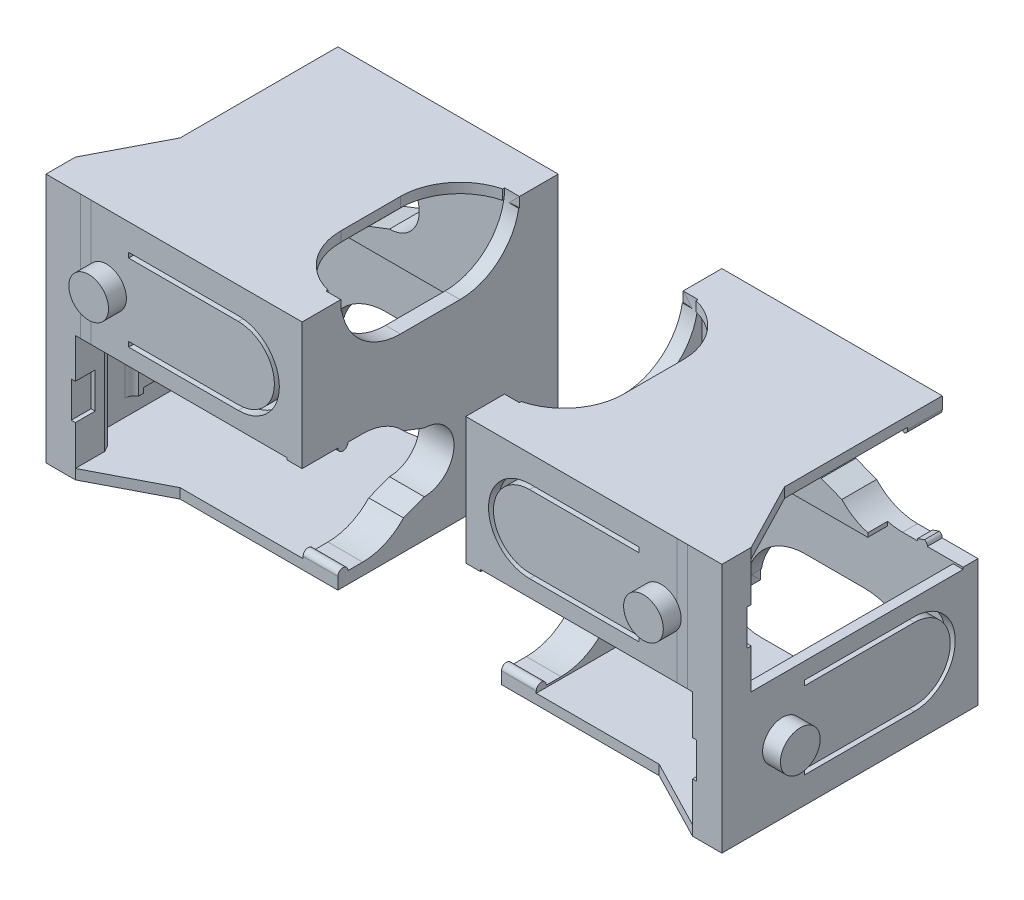
SolidWorks part; units mm, degrees
ref_plane "正面" through (0, 0, 0) normal (0, 0, 1) x (1, 0, 0)
ref_plane "平面" through (0, 0, 0) normal (0, 1, 0) x (1, 0, 0)
ref_plane "右側面" through (0, 0, 0) normal (1, 0, 0) x (0, 0, -1)
sketch "ｽｹｯﾁ1" plane through (0, 0, -3.3889) normal (0, 0, -1) x (-1, 0, 0)
  line L1 (-27.9423, 19.7214) -> (-37.3187, 19.7214) construction
  line L2 (-23.8289, 15.9214) -> (-21.7423, 16.7214)
  line L3 (-21.7423, 22.7214) -> (-23.8289, 23.5214)
  line L4 (-23.8289, 15.9214) -> (-21.7423, 16.7214)
  line L5 (-21.7423, 22.7214) -> (-23.8289, 23.5214)
  line L6 (-27.9423, 26.3214) -> (-30.4423, 26.3214)
  line L7 (-27.9423, 26.3214) -> (-8.2423, 26.3214)
  line L8 (-30.4423, 26.3214) -> (-30.4423, 25.3214)
  line L9 (-29.4213, 25.3214) -> (-27.9423, 25.3214)
  line L10 (-30.4423, 13.9214) -> (-30.4423, 14.1214)
  line L11 (-29.4213, 14.1214) -> (-27.9423, 14.1214)
  line L12 (-27.9423, 13.9214) -> (-30.4423, 13.9214)
  line L13 (-11.7423, 13.9214) -> (-32.5423, 13.9214) construction
  line L14 (-8.2423, 13.9214) -> (-8.2423, 25.5214)
  line L15 (-8.2423, 25.5214) -> (-8.2423, 26.3214)
  line L17 (-33.5423, 13.9214) -> (-9.7423, 13.9214) construction
  line L18 (-27.9423, 13.9214) -> (-9.7423, 13.9214)
  line L20 (-9.7423, 13.9214) -> (-8.2423, 13.9214)
  arc A0 (-27.9423, 14.1214) -> (-23.8289, 15.9214) centre (-27.9423, 19.7214) ccw
  arc A1 (-30.4423, 25.3214) -> (-29.4213, 25.3214) centre (-29.9318, 25.3214) ccw
  arc A2 (-23.8289, 23.5214) -> (-23.8289, 15.9214) centre (-27.9423, 19.7214) ccw
  arc A3 (-21.7423, 16.7214) -> (-21.7423, 22.7214) centre (-21.7423, 19.7214) ccw
  arc A4 (-23.8289, 23.5214) -> (-27.9423, 25.3214) centre (-27.9423, 19.7214) ccw
  arc A5 (-21.7423, 16.7214) -> (-21.7423, 22.7214) centre (-21.7423, 19.7214) ccw
  arc A6 (-30.4423, 14.1214) -> (-29.4213, 14.1214) centre (-29.9318, 14.1214) cw
  dimension "D1" = 0
extrude "ﾎﾞｽ - 押し出し1" add sketch "ｽｹｯﾁ1" against normal up to surface (3.5 mm away)
sketch "ｽｹｯﾁ2" plane through (0, 0, -3.3889) normal (0, 0, -1) x (-1, 0, 0)
  line L0 (-8.2423, 13.9214) -> (-8.2423, 26.3214) construction
  line L1 (-34.0423, 13.9214) -> (-8.2423, 13.9214)
  line L2 (-34.0423, 13.9214) -> (-34.0423, 1.3214)
  line L3 (-34.0423, 1.3214) -> (-8.2423, 1.3214)
  line L4 (-8.2423, 13.9214) -> (-8.2423, 1.3214)
  line L5 (-11.7423, 2.3214) -> (-32.5423, 2.3214) construction
  line L6 (-32.5423, 2.3214) -> (-32.5423, 13.9214) construction
  line L7 (-32.5423, 2.3214) -> (-32.5423, 13.9214) construction
  dimension "D1" = 0
  dimension "D2" = 1
  dimension "D3" = 1.5
extrude "ﾎﾞｽ - 押し出し2" add sketch "ｽｹｯﾁ2" against normal up to vertex (1.5 mm away)
sketch "ｽｹｯﾁ3" plane through (8.2423, 0, 0) normal (-1, 0, 0) x (0, 0, 1)
  line L0 (16.3111, 8.1214) -> (25.6875, 8.1214) construction
  line L1 (12.1977, 11.9214) -> (10.1111, 11.1214)
  line L2 (10.1111, 5.1214) -> (12.1977, 4.3214)
  line L3 (16.3111, 1.5214) -> (18.8111, 1.5214)
  line L4 (16.3111, 1.5214) -> (-3.3889, 1.5214)
  line L5 (18.8111, 1.5214) -> (18.8111, 2.5214)
  line L6 (17.7901, 2.5214) -> (16.3111, 2.5214)
  line L7 (18.8111, 13.9214) -> (18.8111, 13.7214)
  line L8 (17.7901, 13.7214) -> (16.3111, 13.7214)
  line L9 (16.3111, 13.9214) -> (18.8111, 13.9214)
  line L10 (-3.3889, 13.9214) -> (-3.3889, 2.3214)
  line L11 (-3.3889, 2.3214) -> (-3.3889, 1.5214)
  line L12 (16.3111, 13.9214) -> (-1.8889, 13.9214)
  line L13 (-1.8889, 13.9214) -> (-3.3889, 13.9214)
  arc A0 (16.3111, 13.7214) -> (12.1977, 11.9214) centre (16.3111, 8.1214) ccw
  arc A1 (18.8111, 2.5214) -> (17.7901, 2.5214) centre (18.3006, 2.5214) ccw
  arc A2 (12.1977, 4.3214) -> (16.3111, 2.5214) centre (16.3111, 8.1214) ccw
  arc A3 (10.1111, 11.1214) -> (10.1111, 5.1214) centre (10.1111, 8.1214) ccw
  arc A4 (18.8111, 13.7214) -> (17.7901, 13.7214) centre (18.3006, 13.7214) cw
extrude "ﾎﾞｽ - 押し出し3" add sketch "ｽｹｯﾁ3" against normal up to vertex (3.5 mm away)
sketch "ｽｹｯﾁ4" plane through (8.2423, 0, 0) normal (-1, 0, 0) x (0, 0, 1)
  line L0 (0.1111, 26.3214) -> (-3.3889, 26.3214) construction
  line L1 (-1.6389, 26.3214) -> (22.4111, 26.3214)
  line L2 (-1.6389, 26.3214) -> (-1.6389, 13.9214)
  line L3 (-1.6389, 13.9214) -> (22.4111, 13.9214)
  line L4 (22.4111, 26.3214) -> (22.4111, 13.9214)
extrude "ﾎﾞｽ - 押し出し4" add sketch "ｽｹｯﾁ4" against normal up to vertex (1.5 mm away)
sketch "ｽｹｯﾁ5" plane through (0, 0, -1.8889) normal (0, 0, 1) x (1, 0, 0)
  line L0 (34.0423, 13.9214) -> (34.0423, 1.3214) construction
  line L1 (34.0423, 13.9214) -> (34.0423, 1.3214)
  line L2 (32.5423, 2.3214) -> (32.5423, 13.9214) construction
  line L3 (32.5423, 2.3214) -> (32.5423, 13.9214)
  line L4 (32.5423, 13.9214) -> (34.0423, 13.9214)
  line L5 (32.5423, 2.3214) -> (32.5423, 1.3214)
  line L6 (34.0423, 1.3214) -> (32.5423, 1.3214)
  line L7 (34.0423, 1.3214) -> (8.2423, 1.3214) construction
extrude "ﾎﾞｽ - 押し出し5" add sketch "ｽｹｯﾁ5" along normal up to vertex (18.6 mm away)
sketch "ｽｹｯﾁ6" plane through (0, 1.3214, 0) normal (0, -1, 0) x (1, 0, 0)
  line L0 (34.0423, 17.8804) -> (34.0423, 18.9474)
  line L1 (32.5423, 16.7111) -> (29.7774, 21.9111) construction
  line L2 (29.7774, 21.9111) -> (11.7423, 21.9111) construction
  line L3 (33.5423, 19.4468) -> (34.0423, 18.9474) construction
  line L4 (28.3423, 20.9111) -> (33.5423, 18.1462) construction
  line L5 (33.5423, 18.1462) -> (34.0423, 17.8804)
  line L6 (31.0752, 21.9111) -> (30.5752, 22.4105) construction
  line L7 (31.0752, 21.9111) -> (33.5423, 19.4468) construction
  line L8 (29.7774, 21.9111) -> (31.0844, 19.4531)
  line L9 (31.0844, 19.4531) -> (33.5423, 18.1462)
  line L10 (30.5752, 22.4105) -> (34.0423, 22.4105)
  line L11 (34.0423, 18.9474) -> (34.0423, 22.4105)
  line L12 (31.0844, 19.4531) -> (32.3088, 20.679) construction
  line L13 (29.7774, 21.9111) -> (29.5126, 22.4093)
  line L15 (29.5126, 22.4093) -> (30.5752, 22.4105)
extrude "ﾎﾞｽ - 押し出し6" add sketch "ｽｹｯﾁ6" against normal up to vertex (25 mm away) separate body
sketch "ｽｹｯﾁ7" plane through (0, 0, 16.7111) normal (0, 0, 1) x (1, 0, 0)
  line L4 (34.0423, 13.9214) -> (32.5423, 13.9214)
  line L5 (32.5423, 13.9214) -> (32.5423, 1.3214)
  line L6 (32.5423, 1.3214) -> (34.0423, 1.3214)
  line L7 (34.0423, 1.3214) -> (34.0423, 13.9214)
  line L8 (34.0423, 13.9214) -> (32.5423, 13.9214)
  line L9 (32.5423, 13.9214) -> (32.5423, 1.3214)
  line L10 (32.5423, 1.3214) -> (34.0423, 1.3214)
  line L11 (34.0423, 1.3214) -> (34.0423, 13.9214)
  dimension "D1" = 0
extrude "ﾎﾞｽ - 押し出し7" add sketch "ｽｹｯﾁ7" along normal up to next
sketch "ｽｹｯﾁ8" plane through (9.7423, 0, 0) normal (1, 0, 0) x (0, 0, -1)
  line L2 (-22.4111, 13.9214) -> (-22.4111, 26.3214) construction
  line L3 (-20.9111, 25.5214) -> (-20.9111, 13.9214) construction
  line L4 (-22.4111, 13.9214) -> (-22.4111, 26.3214)
  line L5 (-20.9111, 25.5214) -> (-20.9111, 13.9214)
  line L6 (-22.4111, 13.9214) -> (-20.9111, 13.9214)
  line L7 (-22.4111, 26.3214) -> (-20.9111, 26.3214)
  line L9 (-20.9111, 26.3214) -> (-20.9111, 25.5214)
extrude "ﾎﾞｽ - 押し出し8" add sketch "ｽｹｯﾁ8" along normal up to surface (19.7693 mm away)
sketch "ｽｹｯﾁ9" plane through (34.0423, 0, 0) normal (1, 0, 0) x (0, 0, -1)
  circle A1 centre (-16.3111, 8.1214) radius 2
extrude "ﾎﾞｽ - 押し出し9" add sketch "ｽｹｯﾁ9" along normal blind 1.8
sketch "ｽｹｯﾁ10" plane through (0, 0, 22.4111) normal (0, 0, 1) x (1, 0, 0)
  circle A0 centre (27.9423, 19.7214) radius 2 construction
  circle A1 centre (27.9423, 19.7214) radius 2
extrude "ﾎﾞｽ - 押し出し10" add sketch "ｽｹｯﾁ10" along normal blind 1.8
sketch "ｽｹｯﾁ11" plane through (34.0423, 0, 0) normal (1, 0, 0) x (0, 0, -1)
  line L0 (-17.8804, 26.3214) -> (-17.8804, 13.9214) construction
  line L1 (-19.8804, 21.5214) -> (-17.8804, 21.5214)
  line L2 (-19.8804, 21.5214) -> (-19.8804, 17.9214)
  line L3 (-19.8804, 17.9214) -> (-17.8804, 17.9214)
  line L4 (-17.8804, 21.5214) -> (-17.8804, 17.9214)
  line L5 (-18.1462, 13.9214) -> (-0.1111, 13.9214)
  line L6 (-0.1111, 13.9214) -> (-0.1111, 19.7214)
  line L7 (-0.1111, 19.7214) -> (-0.1111, 25.5214)
  line L8 (-0.1111, 25.5214) -> (-18.1462, 25.5214)
  line L9 (-18.1462, 25.5214) -> (-18.1462, 13.9214)
  line L10 (-18.1462, 13.9214) -> (-0.1111, 13.9214) construction
  line L11 (-0.1111, 13.9214) -> (-0.1111, 19.7214) construction
  line L12 (-0.1111, 19.7214) -> (-0.1111, 25.5214) construction
  line L13 (-0.1111, 25.5214) -> (-18.1462, 25.5214) construction
  line L14 (-18.1462, 25.5214) -> (-18.1462, 13.9214) construction
  line L15 (-18.1462, 19.7214) -> (-0.1111, 19.7214) construction
  dimension "D2" = 2
  dimension "D3" = 1.8
  dimension "D4" = 1.8
  dimension "D1" = 0
extrude "ｶｯﾄ - 押し出し1" cut sketch "ｽｹｯﾁ11" against normal blind 2
sketch "ｽｹｯﾁ12" plane through (-0.0262, 0, 22.3746) normal (-0.0012, 0, 1) x (1, 0, 0.0012)
  line L0 (31.5225, 6.3214) -> (29.5225, 6.3214)
  line L1 (31.5225, 6.3214) -> (31.5225, 9.9214)
  line L2 (31.5225, 9.9214) -> (29.5225, 9.9214)
  line L3 (29.5225, 6.3214) -> (29.5225, 9.9214)
  line L4 (29.7884, 13.9214) -> (11.7532, 13.9214) construction
  line L5 (11.7532, 13.9214) -> (11.7532, 8.1214) construction
  line L6 (11.7532, 8.1214) -> (11.7532, 2.3214) construction
  line L7 (11.7532, 2.3214) -> (29.7884, 2.3214) construction
  line L8 (29.7884, 2.3214) -> (29.7884, 13.9214) construction
  line L9 (29.7884, 8.1214) -> (11.7532, 8.1214) construction
extrude "ｶｯﾄ - 押し出し2" cut sketch "ｽｹｯﾁ12" against normal blind 2
sketch "ｽｹｯﾁ13" plane through (32.5423, 0, 0) normal (-1, 0, 0) x (0, 0, 1)
  line L0 (18.6779, 1.3214) -> (-1.8889, 1.3214) construction
  line L1 (-1.8889, 13.9214) -> (-1.8889, 1.3214) construction
  line L2 (-1.8889, 2.3214) -> (16.7111, 2.3214) construction
  line L3 (18.6779, 1.3214) -> (-1.8889, 1.3214)
  line L4 (-1.8889, 2.3214) -> (-1.8889, 1.3214)
  line L5 (-1.8889, 2.3214) -> (16.7111, 2.3214)
  line L6 (18.8111, 1.5214) -> (18.8111, 2.5214) construction
  line L8 (18.8111, 1.5214) -> (18.8111, 2.3214)
  line L9 (16.7111, 2.3214) -> (18.8111, 2.3214)
  line L10 (18.8111, 1.5214) -> (18.8111, 1.3214)
  line L11 (19.4531, 1.3214) -> (18.6779, 1.3214) construction
  line L12 (18.8111, 1.3214) -> (18.6779, 1.3214)
extrude "ﾎﾞｽ - 押し出し11" add sketch "ｽｹｯﾁ13" along normal up to vertex
sketch "ｽｹｯﾁ14" plane through (0, 0, 20.9111) normal (0, 0, -1) x (-1, 0, 0)
  line L0 (-30.4423, 26.3214) -> (-30.4423, 25.3214) construction
  line L1 (-30.3091, 26.3214) -> (-9.7423, 26.3214) construction
  line L2 (-9.7423, 13.9214) -> (-9.7423, 26.3214) construction
  line L3 (-9.7423, 25.5214) -> (-28.3423, 25.5214) construction
  line L4 (-30.4423, 26.3214) -> (-30.4423, 25.5214)
  line L5 (-30.3091, 26.3214) -> (-9.7423, 26.3214)
  line L6 (-9.7423, 25.5214) -> (-9.7423, 26.3214)
  line L7 (-9.7423, 25.5214) -> (-28.3423, 25.5214)
  line L8 (-30.3091, 26.3214) -> (-30.4423, 26.3214)
  line L9 (-28.3423, 25.5214) -> (-30.4423, 25.5214)
extrude "ﾎﾞｽ - 押し出し12" add sketch "ｽｹｯﾁ14" along normal up to vertex (20.8 mm away)
sketch "ｽｹｯﾁ15" plane through (0, 26.3214, 0) normal (0, 1, 0) x (1, 0, 0)
  line L0 (31.0844, -19.4531) -> (34.0423, -19.4531)
  line L1 (31.0844, -19.4531) -> (34.0423, -17.8804) construction
  line L2 (34.0423, -17.8804) -> (34.0423, -22.4105) construction
  line L3 (31.0844, -19.4531) -> (34.0423, -17.8804)
  line L4 (34.0423, -17.8804) -> (34.0423, -19.4531)
extrude "ｶｯﾄ - 押し出し3" cut sketch "ｽｹｯﾁ15" against normal up to vertex
sketch "ｽｹｯﾁ16" plane through (0, 1.3214, 0) normal (0, -1, 0) x (1, 0, 0)
  line L0 (29.5126, 22.4093) -> (31.0844, 19.4531) construction
  line L1 (29.5126, 22.4093) -> (31.0844, 19.4531)
  line L4 (31.0844, 19.4531) -> (31.0844, 22.4105)
  line L5 (34.0423, 22.4105) -> (30.5752, 22.4105) construction
  line L6 (29.5126, 22.4093) -> (30.5752, 22.4105) construction
  line L7 (31.0844, 22.4105) -> (30.5752, 22.4105)
  line L8 (29.5126, 22.4093) -> (30.5752, 22.4105)
extrude "ｶｯﾄ - 押し出し4" cut sketch "ｽｹｯﾁ16" against normal up to vertex
sketch "ｽｹｯﾁ18" plane through (0, 1.3214, 0) normal (0, -1, 0) x (1, 0, 0)
  line L0 (8.2423, 18.8111) -> (32.2919, 18.8111) construction
  line L1 (31.4257, 18.8111) -> (32.2919, 18.8111)
  line L3 (32.2919, 18.8111) -> (31.0844, 19.4531)
  line L5 (32.5423, 16.7111) -> (29.7774, 21.9111) construction
  line L6 (31.4257, 18.8111) -> (31.0844, 19.4531)
extrude "ﾎﾞｽ - 押し出し15" add sketch "ｽｹｯﾁ18" against normal up to vertex
sketch "ｽｹｯﾁ19" plane through (0, 26.3214, 0) normal (0, 1, 0) x (1, 0, 0)
  line L0 (30.4423, -20.6606) -> (31.0844, -19.4531)
  line L2 (30.4423, -20.6606) -> (30.4423, 3.3889) construction
  line L3 (30.4423, -20.6606) -> (30.4423, -19.7945)
  line L7 (9.7423, -0.1111) -> (9.7423, -20.9111)
  line L8 (9.7423, -20.9111) -> (28.3423, -20.9111)
  line L9 (28.3423, -20.9111) -> (33.5423, -18.1462)
  line L10 (33.5423, -18.1462) -> (33.5423, -0.1111)
  line L11 (33.5423, -0.1111) -> (9.7423, -0.1111)
  line L14 (30.4423, -19.7945) -> (31.0844, -19.4531)
  dimension "D1" = 0
extrude "ﾎﾞｽ - 押し出し16" add sketch "ｽｹｯﾁ19" against normal up to vertex
sketch "ｽｹｯﾁ20" plane through (0, 26.3214, 0) normal (0, 1, 0) x (1, 0, 0)
  line L0 (34.0423, -19.4531) -> (30.4423, -12.4985)
  line L1 (30.4423, -19.7945) -> (30.4423, 3.3889) construction
  line L2 (31.0844, -19.4531) -> (34.0423, -19.4531) construction
  line L3 (31.0844, -19.4531) -> (30.4423, -19.7945) construction
  line L4 (30.4423, -19.7945) -> (30.4423, -12.4985)
  line L5 (31.0844, -19.4531) -> (34.0423, -19.4531)
  line L6 (31.0844, -19.4531) -> (30.4423, -19.7945)
extrude "ﾎﾞｽ - 押し出し17" add sketch "ｽｹｯﾁ20" against normal up to vertex
sketch "ｽｹｯﾁ21" plane through (0, 1.3214, 0) normal (0, -1, 0) x (1, 0, 0)
  line L0 (31.0844, 22.4111) -> (24.1297, 18.8111)
  line L1 (31.4257, 18.8111) -> (24.1297, 18.8111)
  line L2 (31.0844, 19.4531) -> (31.0844, 22.4111)
  line L4 (31.0844, 19.4531) -> (31.4257, 18.8111) construction
  line L5 (31.0844, 19.4531) -> (31.4257, 18.8111)
extrude "ﾎﾞｽ - 押し出し18" add sketch "ｽｹｯﾁ21" against normal up to vertex
fillet "ﾌｨﾚｯﾄ1" [suppressed] radius 3
sketch "ｽｹｯﾁ22" plane through (0, 1.3214, 0) normal (0, -1, 0) x (1, 0, 0)
  line L6 (34.0423, 22.4105) -> (31.0844, 22.4105)
  line L7 (34.0423, 22.4105) -> (31.0844, 22.4105)
  line L8 (31.0844, 22.4105) -> (31.0844, 22.4111)
  line L9 (31.0844, 22.4105) -> (31.0844, 22.4111)
  line L10 (31.0844, 22.4111) -> (24.1297, 18.8111)
  line L11 (8.2423, 18.8111) -> (8.2423, -3.3889)
  line L12 (8.2423, -3.3889) -> (34.0423, -3.3889)
  line L13 (34.0423, -3.3889) -> (34.0423, 22.4105)
  line L14 (31.0844, 22.4111) -> (24.1297, 18.8111)
  line L16 (24.1297, 18.8111) -> (8.2423, 18.8111)
  line L17 (24.1297, 18.8111) -> (8.2423, 18.8111)
  line L18 (8.2423, 18.8111) -> (8.2423, -3.3889)
  line L19 (8.2423, -3.3889) -> (34.0423, -3.3889)
  line L20 (34.0423, -3.3889) -> (34.0423, 22.4105)
  dimension "D1" = 0
sketch "ｽｹｯﾁ24" plane through (30.4423, 0, 0) normal (1, 0, 0) x (0, 0, -1)
  line L0 (1.8889, 13.9214) -> (1.8889, 14.1214)
  line L1 (-0.1111, 14.5787) -> (3.3889, 14.5787) construction
  line L2 (-0.1111, 14.5787) -> (1.8889, 14.5787)
  line L3 (1.8889, 14.1214) -> (1.8889, 14.5787)
  line L4 (-0.1111, 14.1214) -> (-0.1111, 14.5787)
  line L5 (-0.1111, 14.1214) -> (-0.1111, 13.9214)
  line L6 (-0.1111, 13.9214) -> (1.8889, 13.9214)
  line L7 (1.8889, 13.9214) -> (3.3889, 13.9214)
  line L8 (3.3889, 13.9214) -> (3.3889, 14.1214)
  line L9 (3.3889, 14.1214) -> (-0.1111, 14.1214)
  line L10 (-0.1111, 14.1214) -> (-0.1111, 13.9214)
  line L11 (-0.1111, 13.9214) -> (1.8889, 13.9214)
  dimension "D1" = 0
extrude "ｶｯﾄ - 押し出し5" cut sketch "ｽｹｯﾁ24" against normal blind 4
sketch "ｽｹｯﾁ25" plane through (30.4423, 0, 0) normal (1, 0, 0) x (0, 0, -1)
  line L4 (3.3889, 14.1214) -> (1.8889, 14.1214)
  line L5 (1.8889, 14.1214) -> (1.8889, 13.9214)
  line L6 (1.8889, 13.9214) -> (3.3889, 13.9214)
  line L7 (3.3889, 13.9214) -> (3.3889, 14.1214)
  line L8 (3.3889, 14.1214) -> (1.8889, 14.1214)
  line L9 (1.8889, 14.1214) -> (1.8889, 13.9214)
  line L10 (1.8889, 13.9214) -> (3.3889, 13.9214)
  line L11 (3.3889, 13.9214) -> (3.3889, 14.1214)
  dimension "D1" = 0
extrude "ﾎﾞｽ - 押し出し21" add sketch "ｽｹｯﾁ25" along normal up to vertex
sketch "ｽｹｯﾁ26" plane through (0, 26.3214, 0) normal (0, 1, 0) x (1, 0, 0)
  line L6 (34.0423, -19.4531) -> (30.4423, -12.4985)
  line L7 (34.0423, -19.4531) -> (30.4423, -12.4985)
  line L8 (29.5116, -22.4111) -> (29.5126, -22.4093)
  line L9 (29.5116, -22.4111) -> (29.5126, -22.4093)
  line L10 (30.4423, -12.4985) -> (30.4423, 3.3889)
  line L11 (30.4423, 3.3889) -> (8.2423, 3.3889)
  line L12 (8.2423, 3.3889) -> (8.2423, -22.4111)
  line L13 (8.2423, -22.4111) -> (29.5116, -22.4111)
  line L17 (29.5126, -22.4093) -> (30.5752, -22.4105)
  line L18 (29.5126, -22.4093) -> (30.5752, -22.4105)
  line L19 (30.4423, -12.4985) -> (30.4423, 3.3889)
  line L20 (30.4423, 3.3889) -> (8.2423, 3.3889)
  line L21 (8.2423, 3.3889) -> (8.2423, -22.4111)
  line L22 (8.2423, -22.4111) -> (29.5116, -22.4111)
  line L23 (30.5752, -22.4105) -> (34.0423, -22.4105)
  line L24 (30.5752, -22.4105) -> (34.0423, -22.4105)
  line L25 (34.0423, -22.4105) -> (34.0423, -19.4531)
  line L26 (34.0423, -22.4105) -> (34.0423, -19.4531)
  dimension "D1" = 0
extrude "ﾎﾞｽ - 押し出し22" add sketch "ｽｹｯﾁ26" along normal blind 0.2
sketch "ｽｹｯﾁ28" plane through (0, 0, 18.8111) normal (0, 0, 1) x (1, 0, 0)
  line L0 (9.7423, 13.9214) -> (9.7423, 13.2109)
  line L1 (8.2423, 13.2109) -> (11.7423, 13.2109) construction
  line L2 (9.7423, 13.2109) -> (11.7423, 13.2109)
  line L3 (11.7423, 13.7214) -> (11.7423, 13.2109)
  line L5 (8.2423, 13.9214) -> (8.2423, 13.7214)
  line L6 (8.2423, 13.7214) -> (11.7423, 13.7214)
  line L7 (11.7423, 13.7214) -> (11.7423, 13.9214)
  line L8 (11.7423, 13.9214) -> (9.7423, 13.9214)
  line L9 (9.7423, 13.9214) -> (8.2423, 13.9214)
  line L12 (11.7423, 13.7214) -> (11.7423, 13.9214)
  line L13 (11.7423, 13.9214) -> (9.7423, 13.9214)
  dimension "D1" = 0
extrude "ｶｯﾄ - 押し出し6" cut sketch "ｽｹｯﾁ28" against normal blind 4
sketch "ｽｹｯﾁ29" plane through (0, 0, 18.8111) normal (0, 0, 1) x (1, 0, 0)
  line L4 (9.7423, 13.7214) -> (9.7423, 13.9214)
  line L5 (9.7423, 13.9214) -> (8.2423, 13.9214)
  line L6 (8.2423, 13.9214) -> (8.2423, 13.7214)
  line L7 (8.2423, 13.7214) -> (9.7423, 13.7214)
  line L8 (9.7423, 13.7214) -> (9.7423, 13.9214)
  line L9 (9.7423, 13.9214) -> (8.2423, 13.9214)
  line L10 (8.2423, 13.9214) -> (8.2423, 13.7214)
  line L11 (8.2423, 13.7214) -> (9.7423, 13.7214)
  dimension "D1" = 0
extrude "ﾎﾞｽ - 押し出し24" add sketch "ｽｹｯﾁ29" along normal up to vertex
sketch "ｽｹｯﾁ30" plane through (8.2423, 0, 0) normal (-1, 0, 0) x (0, 0, 1)
  line L0 (6.5111, 26.5214) -> (12.5111, 26.5214) construction
  line L1 (-3.3889, 26.5214) -> (22.4111, 26.5214) construction
  line L3 (6.5111, 20.5214) -> (12.5111, 20.5214)
  line L4 (0.5111, 26.5214) -> (18.5111, 26.5214)
  arc A0 (0.5111, 26.5214) -> (6.5111, 20.5214) centre (6.5111, 26.5214) ccw
  arc A1 (12.5111, 20.5214) -> (18.5111, 26.5214) centre (12.5111, 26.5214) ccw
  point P4 (9.5111, 26.5214)
  dimension "D2" = 6
  dimension "D1" = 3
extrude "ｶｯﾄ - 押し出し7" cut sketch "ｽｹｯﾁ30" against normal up to vertex (1.5 mm away)
sketch "ｽｹｯﾁ31" plane through (0, 26.5214, 0) normal (0, 1, 0) x (1, 0, 0)
  line L0 (8.2423, -0.5111) -> (8.2423, -18.5111) construction
  line L1 (8.2423, -12.5111) -> (8.2423, -6.5111) construction
  line L2 (2.2423, -12.5111) -> (2.2423, -6.5111)
  line L3 (14.2423, -12.5111) -> (14.2423, -6.5111)
  arc A0 (2.2423, -12.5111) -> (14.2423, -12.5111) centre (8.2423, -12.5111) ccw
  arc A1 (14.2423, -6.5111) -> (2.2423, -6.5111) centre (8.2423, -6.5111) ccw
  point P6 (8.2423, -9.5111)
  dimension "D2" = 6
  dimension "D1" = 3
extrude "ｶｯﾄ - 押し出し8" cut sketch "ｽｹｯﾁ31" against normal up to vertex (1 mm away)
sketch "ｽｹｯﾁ32" plane through (0, 0, -3.3889) normal (0, 0, -1) x (-1, 0, 0)
  line L0 (-34.0423, 1.3214) -> (-8.2423, 1.3214) construction
  line L1 (-24.1423, 1.3214) -> (-18.1423, 1.3214) construction
  line L3 (-24.1423, 7.3214) -> (-18.1423, 7.3214)
  line L4 (-24.1423, -4.6786) -> (-18.1423, -4.6786)
  arc A0 (-24.1423, 7.3214) -> (-24.1423, -4.6786) centre (-24.1423, 1.3214) ccw
  arc A1 (-18.1423, -4.6786) -> (-18.1423, 7.3214) centre (-18.1423, 1.3214) ccw
  point P8 (-21.1423, 1.3214)
  dimension "D1" = 6
extrude "ｶｯﾄ - 押し出し9" cut sketch "ｽｹｯﾁ32" against normal up to vertex (1.5 mm away)
sketch "ｽｹｯﾁ33" plane through (0, 1.3214, 0) normal (0, -1, 0) x (1, 0, 0)
  line L0 (12.1423, -3.3889) -> (30.1423, -3.3889) construction
  line L1 (18.1423, -3.3889) -> (24.1423, -3.3889) construction
  line L2 (18.1423, 2.6111) -> (24.1423, 2.6111)
  line L3 (18.1423, -9.3889) -> (24.1423, -9.3889)
  arc A0 (18.1423, 2.6111) -> (18.1423, -9.3889) centre (18.1423, -3.3889) ccw
  arc A1 (24.1423, -9.3889) -> (24.1423, 2.6111) centre (24.1423, -3.3889) ccw
  point P6 (21.1423, -3.3889)
  dimension "D1" = 6
extrude "ｶｯﾄ - 押し出し10" cut sketch "ｽｹｯﾁ33" against normal up to vertex (1 mm away)
sketch "ｽｹｯﾁ34" plane through (0, 0, 20.9111) normal (0, 0, -1) x (-1, 0, 0)
  line L0 (-25.7146, 19.7214) -> (-14.6711, 19.7214) construction
  line L1 (-25.7146, 23.3566) -> (-14.6711, 23.3566)
  line L2 (-25.7146, 16.0862) -> (-14.6711, 16.0862)
  line L3 (-25.7146, 23.3566) -> (-25.7146, 16.0862) construction
  line L4 (-25.7146, 23.8566) -> (-14.6711, 23.8566)
  line L5 (-25.7146, 15.5862) -> (-14.6711, 15.5862)
  line L6 (-26.2146, 23.8566) -> (-26.2146, 15.5862) construction
  line L7 (-25.7146, 23.3566) -> (-25.7146, 23.8566)
  line L8 (-25.7146, 16.0862) -> (-25.7146, 15.5862)
  line L10 (-26.2146, 23.8566) -> (-14.6711, 23.8566) construction
  line L11 (-26.2146, 15.5862) -> (-14.6711, 15.5862) construction
  arc A0 (-14.6711, 15.5862) -> (-14.6711, 23.8566) centre (-14.6711, 19.7214) ccw
  arc A1 (-14.6711, 16.0862) -> (-14.6711, 23.3566) centre (-14.6711, 19.7214) ccw
  circle A2 centre (-27.9423, 19.7214) radius 2 construction
  circle A3 centre (-27.9423, 19.7214) radius 2 construction
  point P2 (-20.1928, 19.7214)
  dimension "D1" = 0.5
extrude "ｶｯﾄ - 押し出し11" cut sketch "ｽｹｯﾁ34" against normal up to vertex
sketch "ｽｹｯﾁ35" plane through (0, 0, 20.9111) normal (0, 0, -1) x (-1, 0, 0)
  line L0 (-14.6711, 23.8566) -> (-25.7146, 23.8566) construction
  line L1 (-25.7146, 15.5862) -> (-14.6711, 15.5862) construction
  line L2 (-14.6711, 23.8566) -> (-25.7146, 23.8566)
  line L3 (-25.7146, 15.5862) -> (-14.6711, 15.5862)
  line L4 (-9.7423, 25.5214) -> (-30.3091, 25.5214)
  line L5 (-30.3091, 25.5214) -> (-30.3091, 13.9214)
  line L6 (-30.3091, 13.9214) -> (-9.7423, 13.9214)
  line L7 (-9.7423, 13.9214) -> (-9.7423, 25.5214)
  line L8 (-9.7423, 25.5214) -> (-30.3091, 25.5214)
  line L9 (-30.3091, 25.5214) -> (-30.3091, 13.9214)
  line L10 (-30.3091, 13.9214) -> (-9.7423, 13.9214)
  line L11 (-9.7423, 13.9214) -> (-9.7423, 25.5214)
  line L12 (-26.2146, 23.8566) -> (-26.2146, 15.5862)
  line L13 (-26.2146, 15.5862) -> (-25.7146, 15.5862)
  line L14 (-25.7146, 23.8566) -> (-26.2146, 23.8566)
  arc A0 (-14.6711, 15.5862) -> (-14.6711, 23.8566) centre (-14.6711, 19.7214) ccw construction
  arc A1 (-14.6711, 15.5862) -> (-14.6711, 23.8566) centre (-14.6711, 19.7214) ccw
  dimension "D2" = 0.5
  dimension "D1" = 0
extrude "ｶｯﾄ - 押し出し12" cut sketch "ｽｹｯﾁ35" against normal blind 0.5
fillet "ﾌｨﾚｯﾄ2" radius 1 1 edges at (26.2146, 19.7214, 21.4111)
sketch "ｽｹｯﾁ37" plane through (32.5423, 0, 0) normal (-1, 0, 0) x (0, 0, 1)
  line L0 (14.0833, 8.1214) -> (3.0398, 8.1214) construction
  line L1 (14.0833, 4.4862) -> (3.0398, 4.4862)
  line L2 (14.0833, 11.7566) -> (3.0398, 11.7566)
  line L3 (14.0833, 4.4862) -> (14.0833, 11.7566) construction
  line L4 (14.0833, 3.9862) -> (3.0398, 3.9862)
  line L5 (14.0833, 12.2566) -> (3.0398, 12.2566)
  line L6 (14.5833, 3.9862) -> (14.5833, 12.2566) construction
  line L7 (14.0833, 4.4862) -> (14.0833, 3.9862)
  line L8 (14.0833, 11.7566) -> (14.0833, 12.2566)
  line L9 (16.3111, 8.1214) -> (16.3111, 11.2995) construction
  line L10 (16.3111, 8.1214) -> (12.7058, 8.1214) construction
  circle A0 centre (16.3111, 8.1214) radius 2 construction
  circle A1 centre (16.3111, 8.1214) radius 2 construction
  arc A2 (3.0398, 12.2566) -> (3.0398, 3.9862) centre (3.0398, 8.1214) ccw
  arc A3 (3.0398, 11.7566) -> (3.0398, 4.4862) centre (3.0398, 8.1214) ccw
  point P5 (8.5616, 8.1214)
extrude "ｶｯﾄ - 押し出し13" cut sketch "ｽｹｯﾁ37" against normal up to vertex (1.5 mm away) up to point (34.0423, 1.3214, -3.3889)
sketch "ｽｹｯﾁ38" plane through (32.5423, 0, 0) normal (-1, 0, 0) x (0, 0, 1)
  line L0 (14.0833, 12.2566) -> (3.0398, 12.2566) construction
  line L1 (3.0398, 3.9862) -> (14.0833, 3.9862) construction
  line L2 (14.0833, 12.2566) -> (3.0398, 12.2566)
  line L3 (3.0398, 3.9862) -> (14.0833, 3.9862)
  line L4 (-1.8889, 2.3214) -> (18.6779, 2.3214)
  line L5 (18.6779, 2.3214) -> (18.6779, 13.9214)
  line L6 (18.6779, 13.9214) -> (-1.8889, 13.9214)
  line L7 (-1.8889, 13.9214) -> (-1.8889, 2.3214)
  line L8 (-1.8889, 2.3214) -> (18.6779, 2.3214)
  line L9 (18.6779, 2.3214) -> (18.6779, 13.9214)
  line L10 (18.6779, 13.9214) -> (-1.8889, 13.9214)
  line L11 (-1.8889, 13.9214) -> (-1.8889, 2.3214)
  line L12 (14.5833, 12.2566) -> (14.5833, 3.9862)
  line L13 (14.5833, 3.9862) -> (14.0833, 3.9862)
  line L14 (14.0833, 12.2566) -> (14.5833, 12.2566)
  arc A0 (3.0398, 12.2566) -> (3.0398, 3.9862) centre (3.0398, 8.1214) ccw construction
  arc A1 (3.0398, 12.2566) -> (3.0398, 3.9862) centre (3.0398, 8.1214) ccw
  dimension "D2" = 0.5
  dimension "D1" = 0
extrude "ｶｯﾄ - 押し出し14" cut sketch "ｽｹｯﾁ38" against normal blind 0.5
fillet "ﾌｨﾚｯﾄ3" radius 1 1 edges at (33.0423, 8.1214, 14.5833)
mirror "ﾐﾗｰ2" about plane through (0, 0, 0) normal (1, 0, 0) of bodies 143 124
